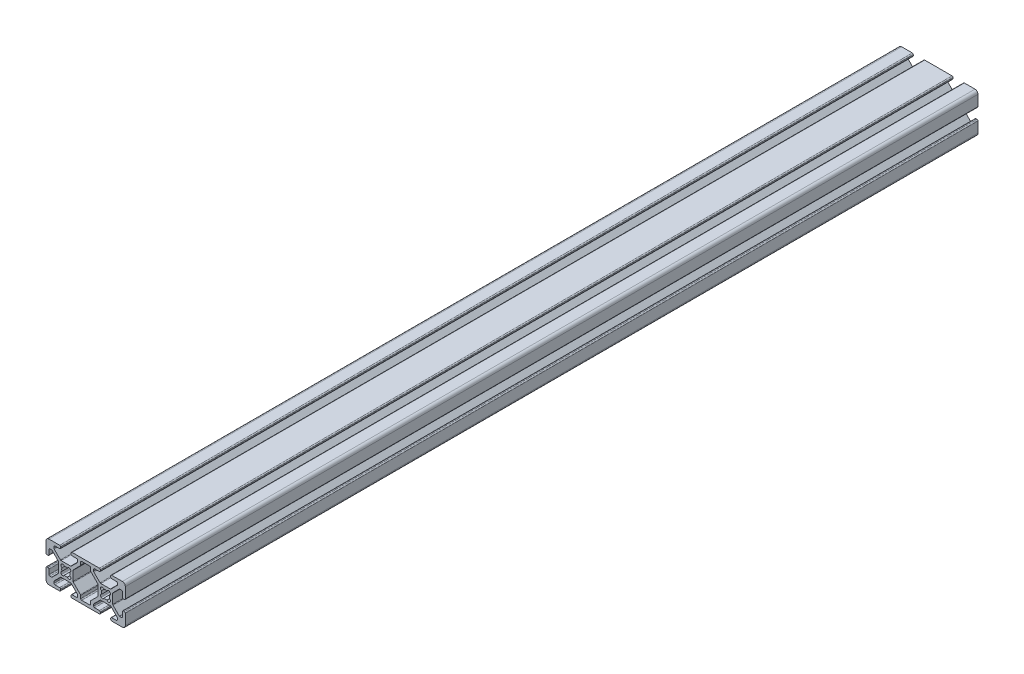
SolidWorks part; units mm, degrees
material "6105-T5 Aluminum"
ref_plane "Front Plane" through (0, 0, 0) normal (0, 0, 1) x (1, 0, 0)
ref_plane "Top Plane" through (0, 0, 0) normal (0, 1, 0) x (1, 0, 0)
ref_plane "Right Plane" through (0, 0, 0) normal (1, 0, 0) x (0, 0, -1)
sketch "Sketch1" plane through (0, 0, 0) normal (0, 0, 1) x (1, 0, 0)
  line L0 (-2.1249, -2.3045) -> (-2.3045, -2.1249)
  line L1 (-2.3045, 2.1249) -> (-2.1249, 2.3045)
  line L2 (2.1249, 2.3045) -> (2.3045, 2.1249)
  line L3 (2.3045, -2.1249) -> (2.1249, -2.3045)
  line L4 (-12.505, -7.992) -> (-12.505, -6.6448)
  line L5 (-12.6538, -6.2856) -> (-16.1962, -2.7431)
  line L6 (-16.345, -2.3839) -> (-16.345, 2.3839)
  line L7 (-16.1962, 2.7431) -> (-12.6538, 6.2856)
  line L8 (-12.505, 6.6448) -> (-12.505, 7.992)
  line L9 (-11.997, 8.5) -> (-8.003, 8.5)
  line L10 (-7.495, 7.992) -> (-7.495, 6.6448)
  line L11 (-7.3462, 6.2856) -> (-3.8038, 2.7431)
  line L12 (-3.655, 2.3839) -> (-3.655, -2.3839)
  line L13 (-3.8038, -2.7431) -> (-7.3462, -6.2856)
  line L14 (-7.495, -6.6448) -> (-7.495, -7.992)
  line L15 (-8.003, -8.5) -> (-11.997, -8.5)
  line L16 (-22.1249, -2.3045) -> (-22.3045, -2.1249)
  line L17 (-22.3045, 2.1249) -> (-22.1249, 2.3045)
  line L18 (-17.8751, 2.3045) -> (-17.6955, 2.1249)
  line L19 (-17.6955, -2.1249) -> (-17.8751, -2.3045)
  line L20 (-22.3839, -3.655) -> (-17.6161, -3.655)
  line L21 (-17.2569, -3.8038) -> (-14.1538, -6.9069)
  line L22 (-14.005, -7.2661) -> (-14.005, -7.992)
  line L23 (-14.513, -8.5) -> (-16.862, -8.5)
  line L24 (-17.37, -9.008) -> (-17.37, -9.492)
  line L25 (-16.862, -10) -> (-3.138, -10)
  line L26 (-2.63, -9.492) -> (-2.63, -9.008)
  line L27 (-3.138, -8.5) -> (-5.487, -8.5)
  line L28 (-5.995, -7.992) -> (-5.995, -7.2661)
  line L29 (-5.8462, -6.9069) -> (-2.7431, -3.8038)
  line L30 (-2.3839, -3.655) -> (2.3839, -3.655)
  line L31 (2.7431, -3.8038) -> (5.8462, -6.9069)
  line L32 (5.995, -7.2661) -> (5.995, -7.992)
  line L33 (5.487, -8.5) -> (3.138, -8.5)
  line L34 (2.63, -9.008) -> (2.63, -9.492)
  line L35 (3.138, -10) -> (8.5, -10)
  line L36 (10, -8.5) -> (10, -3.138)
  line L37 (9.492, -2.63) -> (9.008, -2.63)
  line L38 (8.5, -3.138) -> (8.5, -5.487)
  line L39 (7.992, -5.995) -> (7.2661, -5.995)
  line L40 (6.9069, -5.8462) -> (3.8038, -2.7431)
  line L41 (3.655, -2.3839) -> (3.655, 2.3839)
  line L42 (3.8038, 2.7431) -> (6.9069, 5.8462)
  line L43 (7.2661, 5.995) -> (7.992, 5.995)
  line L44 (8.5, 5.487) -> (8.5, 3.138)
  line L45 (9.008, 2.63) -> (9.492, 2.63)
  line L46 (10, 3.138) -> (10, 8.5)
  line L47 (8.5, 10) -> (3.138, 10)
  line L48 (2.63, 9.492) -> (2.63, 9.008)
  line L49 (3.138, 8.5) -> (5.487, 8.5)
  line L50 (5.995, 7.992) -> (5.995, 7.2661)
  line L51 (5.8462, 6.9069) -> (2.7431, 3.8038)
  line L52 (2.3839, 3.655) -> (-2.3839, 3.655)
  line L53 (-2.7431, 3.8038) -> (-5.8462, 6.9069)
  line L54 (-5.995, 7.2661) -> (-5.995, 7.992)
  line L55 (-5.487, 8.5) -> (-3.138, 8.5)
  line L56 (-2.63, 9.008) -> (-2.63, 9.492)
  line L57 (-3.138, 10) -> (-16.862, 10)
  line L58 (-17.37, 9.492) -> (-17.37, 9.008)
  line L59 (-16.862, 8.5) -> (-14.513, 8.5)
  line L60 (-14.005, 7.992) -> (-14.005, 7.2661)
  line L61 (-14.1538, 6.9069) -> (-17.2569, 3.8038)
  line L62 (-17.6161, 3.655) -> (-22.3839, 3.655)
  line L63 (-22.7431, 3.8038) -> (-25.8462, 6.9069)
  line L64 (-25.995, 7.2661) -> (-25.995, 7.992)
  line L65 (-25.487, 8.5) -> (-23.138, 8.5)
  line L66 (-22.63, 9.008) -> (-22.63, 9.492)
  line L67 (-23.138, 10) -> (-28.5, 10)
  line L68 (-30, 8.5) -> (-30, 3.138)
  line L69 (-29.492, 2.63) -> (-29.008, 2.63)
  line L70 (-28.5, 3.138) -> (-28.5, 5.487)
  line L71 (-27.992, 5.995) -> (-27.2661, 5.995)
  line L72 (-26.9069, 5.8462) -> (-23.8038, 2.7431)
  line L73 (-23.655, 2.3839) -> (-23.655, -2.3839)
  line L74 (-23.8038, -2.7431) -> (-26.9069, -5.8462)
  line L75 (-27.2661, -5.995) -> (-27.992, -5.995)
  line L76 (-28.5, -5.487) -> (-28.5, -3.138)
  line L77 (-29.008, -2.63) -> (-29.492, -2.63)
  line L78 (-30, -3.138) -> (-30, -8.5)
  line L79 (-28.5, -10) -> (-23.138, -10)
  line L80 (-22.63, -9.492) -> (-22.63, -9.008)
  line L81 (-23.138, -8.5) -> (-25.487, -8.5)
  line L82 (-25.995, -7.992) -> (-25.995, -7.2661)
  line L83 (-25.8462, -6.9069) -> (-22.7431, -3.8038)
  arc A0 (-1.9351, -0.804) -> (-2.3045, -2.1249) centre (-1.748, -1.5684) ccw
  arc A1 (-1.9351, 0.804) -> (-1.9351, -0.804) centre (0, 0) ccw
  arc A2 (-2.3045, 2.1249) -> (-1.9351, 0.804) centre (-1.748, 1.5684) ccw
  arc A3 (-0.804, 1.9351) -> (-2.1249, 2.3045) centre (-1.5684, 1.748) ccw
  arc A4 (0.804, 1.9351) -> (-0.804, 1.9351) centre (0, 0) ccw
  arc A5 (2.1249, 2.3045) -> (0.804, 1.9351) centre (1.5684, 1.748) ccw
  arc A6 (1.9351, 0.804) -> (2.3045, 2.1249) centre (1.748, 1.5684) ccw
  arc A7 (1.9351, -0.804) -> (1.9351, 0.804) centre (0, 0) ccw
  arc A8 (2.3045, -2.1249) -> (1.9351, -0.804) centre (1.748, -1.5684) ccw
  arc A9 (0.804, -1.9351) -> (2.1249, -2.3045) centre (1.5684, -1.748) ccw
  arc A10 (-0.804, -1.9351) -> (0.804, -1.9351) centre (0, 0) ccw
  arc A11 (-2.1249, -2.3045) -> (-0.804, -1.9351) centre (-1.5684, -1.748) ccw
  arc A12 (-12.505, -7.992) -> (-11.997, -8.5) centre (-11.997, -7.992) ccw
  arc A13 (-12.505, -6.6448) -> (-12.6538, -6.2856) centre (-13.013, -6.6448) ccw
  arc A14 (-16.345, -2.3839) -> (-16.1962, -2.7431) centre (-15.837, -2.3839) ccw
  arc A15 (-16.1962, 2.7431) -> (-16.345, 2.3839) centre (-15.837, 2.3839) ccw
  arc A16 (-12.6538, 6.2856) -> (-12.505, 6.6448) centre (-13.013, 6.6448) ccw
  arc A17 (-11.997, 8.5) -> (-12.505, 7.992) centre (-11.997, 7.992) ccw
  arc A18 (-7.495, 7.992) -> (-8.003, 8.5) centre (-8.003, 7.992) ccw
  arc A19 (-7.495, 6.6448) -> (-7.3462, 6.2856) centre (-6.987, 6.6448) ccw
  arc A20 (-3.655, 2.3839) -> (-3.8038, 2.7431) centre (-4.163, 2.3839) ccw
  arc A21 (-3.8038, -2.7431) -> (-3.655, -2.3839) centre (-4.163, -2.3839) ccw
  arc A22 (-7.3462, -6.2856) -> (-7.495, -6.6448) centre (-6.987, -6.6448) ccw
  arc A23 (-8.003, -8.5) -> (-7.495, -7.992) centre (-8.003, -7.992) ccw
  arc A24 (-21.9351, -0.804) -> (-22.3045, -2.1249) centre (-21.748, -1.5684) ccw
  arc A25 (-21.9351, 0.804) -> (-21.9351, -0.804) centre (-20, 0) ccw
  arc A26 (-22.3045, 2.1249) -> (-21.9351, 0.804) centre (-21.748, 1.5684) ccw
  arc A27 (-20.804, 1.9351) -> (-22.1249, 2.3045) centre (-21.5684, 1.748) ccw
  arc A28 (-19.196, 1.9351) -> (-20.804, 1.9351) centre (-20, 0) ccw
  arc A29 (-17.8751, 2.3045) -> (-19.196, 1.9351) centre (-18.4316, 1.748) ccw
  arc A30 (-18.0649, 0.804) -> (-17.6955, 2.1249) centre (-18.252, 1.5684) ccw
  arc A31 (-18.0649, -0.804) -> (-18.0649, 0.804) centre (-20, 0) ccw
  arc A32 (-17.6955, -2.1249) -> (-18.0649, -0.804) centre (-18.252, -1.5684) ccw
  arc A33 (-19.196, -1.9351) -> (-17.8751, -2.3045) centre (-18.4316, -1.748) ccw
  arc A34 (-20.804, -1.9351) -> (-19.196, -1.9351) centre (-20, 0) ccw
  arc A35 (-22.1249, -2.3045) -> (-20.804, -1.9351) centre (-21.5684, -1.748) ccw
  arc A36 (-22.3839, -3.655) -> (-22.7431, -3.8038) centre (-22.3839, -4.163) ccw
  arc A37 (-17.2569, -3.8038) -> (-17.6161, -3.655) centre (-17.6161, -4.163) ccw
  arc A38 (-14.005, -7.2661) -> (-14.1538, -6.9069) centre (-14.513, -7.2661) ccw
  arc A39 (-14.513, -8.5) -> (-14.005, -7.992) centre (-14.513, -7.992) ccw
  arc A40 (-16.862, -8.5) -> (-17.37, -9.008) centre (-16.862, -9.008) ccw
  arc A41 (-17.37, -9.492) -> (-16.862, -10) centre (-16.862, -9.492) ccw
  arc A42 (-3.138, -10) -> (-2.63, -9.492) centre (-3.138, -9.492) ccw
  arc A43 (-2.63, -9.008) -> (-3.138, -8.5) centre (-3.138, -9.008) ccw
  arc A44 (-5.995, -7.992) -> (-5.487, -8.5) centre (-5.487, -7.992) ccw
  arc A45 (-5.8462, -6.9069) -> (-5.995, -7.2661) centre (-5.487, -7.2661) ccw
  arc A46 (-2.3839, -3.655) -> (-2.7431, -3.8038) centre (-2.3839, -4.163) ccw
  arc A47 (2.7431, -3.8038) -> (2.3839, -3.655) centre (2.3839, -4.163) ccw
  arc A48 (5.995, -7.2661) -> (5.8462, -6.9069) centre (5.487, -7.2661) ccw
  arc A49 (5.487, -8.5) -> (5.995, -7.992) centre (5.487, -7.992) ccw
  arc A50 (3.138, -8.5) -> (2.63, -9.008) centre (3.138, -9.008) ccw
  arc A51 (2.63, -9.492) -> (3.138, -10) centre (3.138, -9.492) ccw
  arc A52 (8.5, -10) -> (10, -8.5) centre (8.5, -8.5) ccw
  arc A53 (10, -3.138) -> (9.492, -2.63) centre (9.492, -3.138) ccw
  arc A54 (9.008, -2.63) -> (8.5, -3.138) centre (9.008, -3.138) ccw
  arc A55 (7.992, -5.995) -> (8.5, -5.487) centre (7.992, -5.487) ccw
  arc A56 (6.9069, -5.8462) -> (7.2661, -5.995) centre (7.2661, -5.487) ccw
  arc A57 (3.655, -2.3839) -> (3.8038, -2.7431) centre (4.163, -2.3839) ccw
  arc A58 (3.8038, 2.7431) -> (3.655, 2.3839) centre (4.163, 2.3839) ccw
  arc A59 (7.2661, 5.995) -> (6.9069, 5.8462) centre (7.2661, 5.487) ccw
  arc A60 (8.5, 5.487) -> (7.992, 5.995) centre (7.992, 5.487) ccw
  arc A61 (8.5, 3.138) -> (9.008, 2.63) centre (9.008, 3.138) ccw
  arc A62 (9.492, 2.63) -> (10, 3.138) centre (9.492, 3.138) ccw
  arc A63 (10, 8.5) -> (8.5, 10) centre (8.5, 8.5) ccw
  arc A64 (3.138, 10) -> (2.63, 9.492) centre (3.138, 9.492) ccw
  arc A65 (2.63, 9.008) -> (3.138, 8.5) centre (3.138, 9.008) ccw
  arc A66 (5.995, 7.992) -> (5.487, 8.5) centre (5.487, 7.992) ccw
  arc A67 (5.8462, 6.9069) -> (5.995, 7.2661) centre (5.487, 7.2661) ccw
  arc A68 (2.3839, 3.655) -> (2.7431, 3.8038) centre (2.3839, 4.163) ccw
  arc A69 (-2.7431, 3.8038) -> (-2.3839, 3.655) centre (-2.3839, 4.163) ccw
  arc A70 (-5.995, 7.2661) -> (-5.8462, 6.9069) centre (-5.487, 7.2661) ccw
  arc A71 (-5.487, 8.5) -> (-5.995, 7.992) centre (-5.487, 7.992) ccw
  arc A72 (-3.138, 8.5) -> (-2.63, 9.008) centre (-3.138, 9.008) ccw
  arc A73 (-2.63, 9.492) -> (-3.138, 10) centre (-3.138, 9.492) ccw
  arc A74 (-16.862, 10) -> (-17.37, 9.492) centre (-16.862, 9.492) ccw
  arc A75 (-17.37, 9.008) -> (-16.862, 8.5) centre (-16.862, 9.008) ccw
  arc A76 (-14.005, 7.992) -> (-14.513, 8.5) centre (-14.513, 7.992) ccw
  arc A77 (-14.1538, 6.9069) -> (-14.005, 7.2661) centre (-14.513, 7.2661) ccw
  arc A78 (-17.6161, 3.655) -> (-17.2569, 3.8038) centre (-17.6161, 4.163) ccw
  arc A79 (-22.7431, 3.8038) -> (-22.3839, 3.655) centre (-22.3839, 4.163) ccw
  arc A80 (-25.995, 7.2661) -> (-25.8462, 6.9069) centre (-25.487, 7.2661) ccw
  arc A81 (-25.487, 8.5) -> (-25.995, 7.992) centre (-25.487, 7.992) ccw
  arc A82 (-23.138, 8.5) -> (-22.63, 9.008) centre (-23.138, 9.008) ccw
  arc A83 (-22.63, 9.492) -> (-23.138, 10) centre (-23.138, 9.492) ccw
  arc A84 (-28.5, 10) -> (-30, 8.5) centre (-28.5, 8.5) ccw
  arc A85 (-30, 3.138) -> (-29.492, 2.63) centre (-29.492, 3.138) ccw
  arc A86 (-29.008, 2.63) -> (-28.5, 3.138) centre (-29.008, 3.138) ccw
  arc A87 (-27.992, 5.995) -> (-28.5, 5.487) centre (-27.992, 5.487) ccw
  arc A88 (-26.9069, 5.8462) -> (-27.2661, 5.995) centre (-27.2661, 5.487) ccw
  arc A89 (-23.655, 2.3839) -> (-23.8038, 2.7431) centre (-24.163, 2.3839) ccw
  arc A90 (-23.8038, -2.7431) -> (-23.655, -2.3839) centre (-24.163, -2.3839) ccw
  arc A91 (-27.2661, -5.995) -> (-26.9069, -5.8462) centre (-27.2661, -5.487) ccw
  arc A92 (-28.5, -5.487) -> (-27.992, -5.995) centre (-27.992, -5.487) ccw
  arc A93 (-28.5, -3.138) -> (-29.008, -2.63) centre (-29.008, -3.138) ccw
  arc A94 (-29.492, -2.63) -> (-30, -3.138) centre (-29.492, -3.138) ccw
  arc A95 (-30, -8.5) -> (-28.5, -10) centre (-28.5, -8.5) ccw
  arc A96 (-23.138, -10) -> (-22.63, -9.492) centre (-23.138, -9.492) ccw
  arc A97 (-22.63, -9.008) -> (-23.138, -8.5) centre (-23.138, -9.008) ccw
  arc A98 (-25.995, -7.992) -> (-25.487, -8.5) centre (-25.487, -7.992) ccw
  arc A99 (-25.8462, -6.9069) -> (-25.995, -7.2661) centre (-25.487, -7.2661) ccw
extrude "Extrude1" add sketch "Sketch1" against normal blind 430
